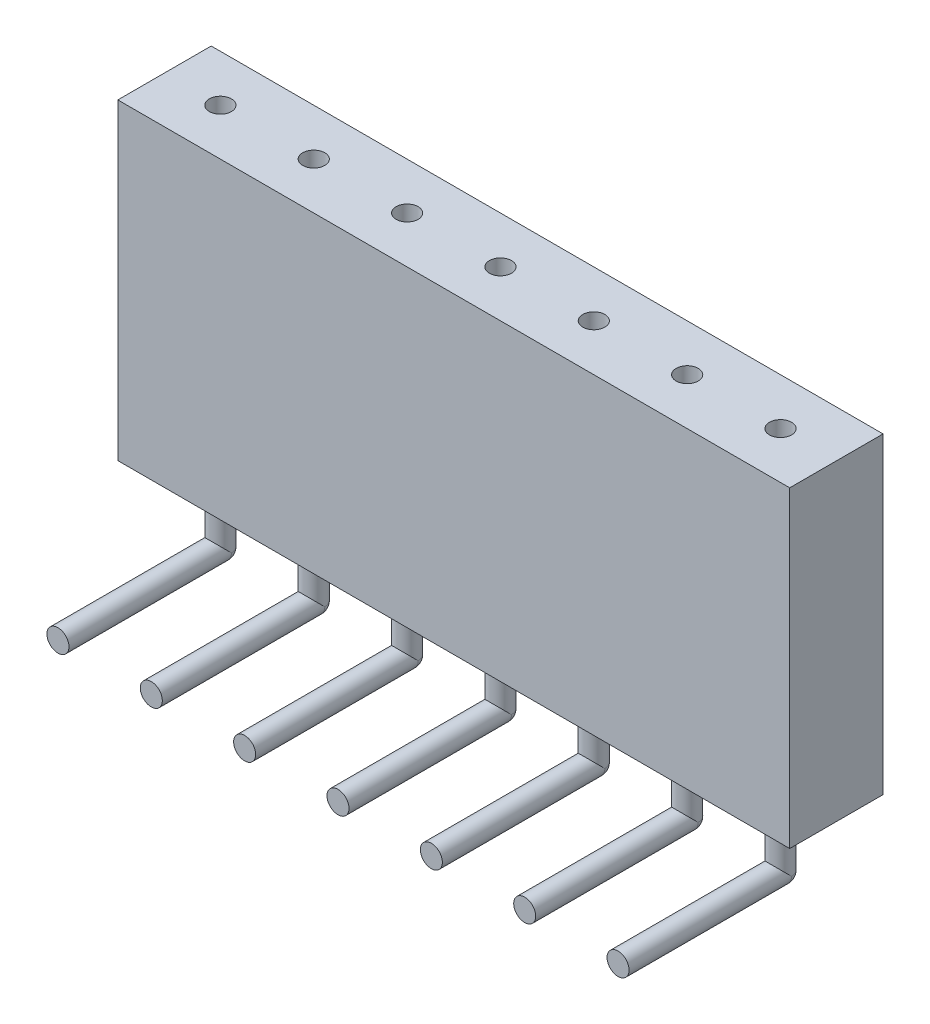
SolidWorks part; units mm, degrees
ref_plane "Спереди" through (0, 0, 0) normal (0, 0, 1) x (1, 0, 0)
ref_plane "Сверху" through (0, 0, 0) normal (0, 1, 0) x (1, 0, 0)
ref_plane "Справа" through (0, 0, 0) normal (1, 0, 0) x (0, 0, -1)
sketch "Эскиз1" plane through (0, 0, 0) normal (0, 1, 0) x (1, 0, 0)
  line L1 (-9.14, 1.27) -> (9.14, 1.27)
  line L2 (-9.14, 1.27) -> (-9.14, -1.27)
  line L3 (-9.14, -1.27) -> (9.14, -1.27)
  line L4 (9.14, 1.27) -> (9.14, -1.27)
  line L5 (-9.14, 1.27) -> (9.14, -1.27) construction
  line L6 (-9.14, -1.27) -> (9.14, 1.27) construction
  point P0 (0, 0)
extrude "Бобышка-Вытянуть1" add sketch "Эскиз1" along normal blind 8.5
sketch "Эскиз2" plane through (0, 8.5, 0) normal (0, 1, 0) x (1, 0, 0)
  circle A0 centre (-7.62, 0) radius 0.3
  circle A1 centre (-5.08, 0) radius 0.3
  circle A2 centre (-2.54, 0) radius 0.3
  circle A3 centre (0, 0) radius 0.3
  circle A4 centre (2.54, 0) radius 0.3
  circle A5 centre (5.08, 0) radius 0.3
  circle A6 centre (7.62, 0) radius 0.3
  dimension "D1" = 7
extrude "Вырез-Вытянуть1" cut sketch "Эскиз2" against normal blind 8.5
sketch "Эскиз3" plane through (0, 0, 0) normal (0, -1, 0) x (1, 0, 0)
  circle A0 centre (-7.62, 0) radius 0.3
  circle A1 centre (-5.08, 0) radius 0.3
  circle A2 centre (-2.54, 0) radius 0.3
  circle A3 centre (0, 0) radius 0.3
  circle A4 centre (2.54, 0) radius 0.3
  circle A5 centre (5.08, 0) radius 0.3
  circle A6 centre (7.62, 0) radius 0.3
  dimension "D1" = 7
extrude "Бобышка-Вытянуть2" add sketch "Эскиз3" along normal blind 1.9 separate body
ref_plane "Плоскость1" through (0, 0, 0) normal (0, 0, 1) x (1, 0, 0)
sketch "Эскиз4" plane through (0, 0, 0) normal (0, 0, 1) x (1, 0, 0)
  circle A0 centre (-7.62, -1.9) radius 0.3
  circle A1 centre (-5.08, -1.9) radius 0.3
  circle A2 centre (-2.54, -1.9) radius 0.3
  circle A3 centre (0, -1.9) radius 0.3
  circle A4 centre (2.54, -1.9) radius 0.3
  circle A5 centre (5.08, -1.9) radius 0.3
  circle A6 centre (7.62, -1.9) radius 0.3
extrude "Бобышка-Вытянуть3" add sketch "Эскиз4" along normal blind 4.42 and the other way blind 0.3 separate body
fillet "Скругление2" radius 0.3 1 edges at (-7.32, -1.9, -0.3)
fillet "Скругление3" radius 0.3 1 edges at (-4.78, -1.9, -0.3)
fillet "Скругление4" radius 0.3 1 edges at (-2.24, -1.9, -0.3)
fillet "Скругление5" radius 0.3 1 edges at (0.3, -1.9, -0.3)
fillet "Скругление6" radius 0.3 1 edges at (2.84, -1.9, -0.3)
fillet "Скругление7" radius 0.3 1 edges at (5.38, -1.9, -0.3)
fillet "Скругление8" radius 0.3 1 edges at (7.92, -1.9, -0.3)
